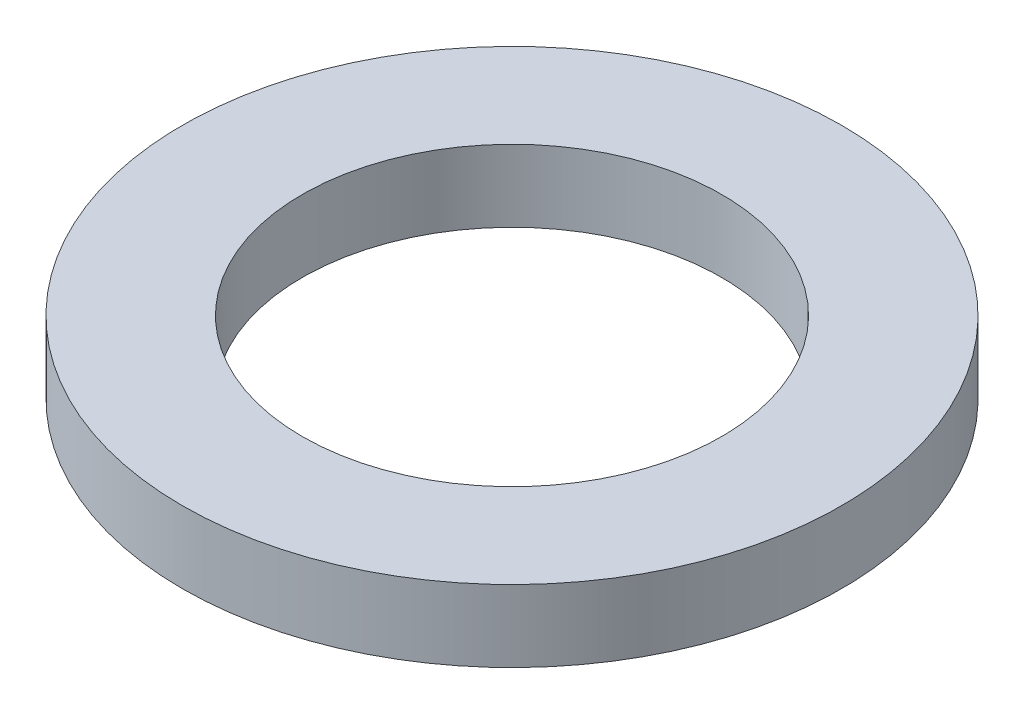
SolidWorks part; units mm, degrees
ref_plane "Front Plane" through (0, 0, 0) normal (0, 0, 1) x (1, 0, 0)
ref_plane "Top Plane" through (0, 0, 0) normal (0, 1, 0) x (1, 0, 0)
ref_plane "Right Plane" through (0, 0, 0) normal (1, 0, 0) x (0, 0, -1)
sketch "Sketch1" plane through (0, 0, 0) normal (0, 1, 0) x (1, 0, 0)
  circle A0 centre (0, 0) radius 27.5
  dimension "FLANGE_OD" = 55
extrude "Boss-Extrude1" add sketch "Sketch1" along normal blind 6
sketch "Sketch2" plane through (0, 0, 0) normal (0, 1, 0) x (1, 0, 0)
  circle A0 centre (0, 0) radius 17.5
  dimension "BORE_D" = 35
extrude "Cut-Extrude1" cut sketch "Sketch2" along normal through all
sketch "Sketch3" plane through (0, 6, 0) normal (0, 1, 0) x (1, 0, 0)
  circle A0 centre (0, 0) radius 10.4847 construction
  circle A1 centre (-10.4847, 0) radius 1.7969
  dimension "BOLT_D" = 3.5939
  dimension "BOLT_PCD" = 20.9694
extrude "Cut-Extrude2" cut sketch "Sketch3" against normal blind 5.7629 rebuild error yes
pattern_circular "CirPattern1" count 3 over 360 rebuild error yes
